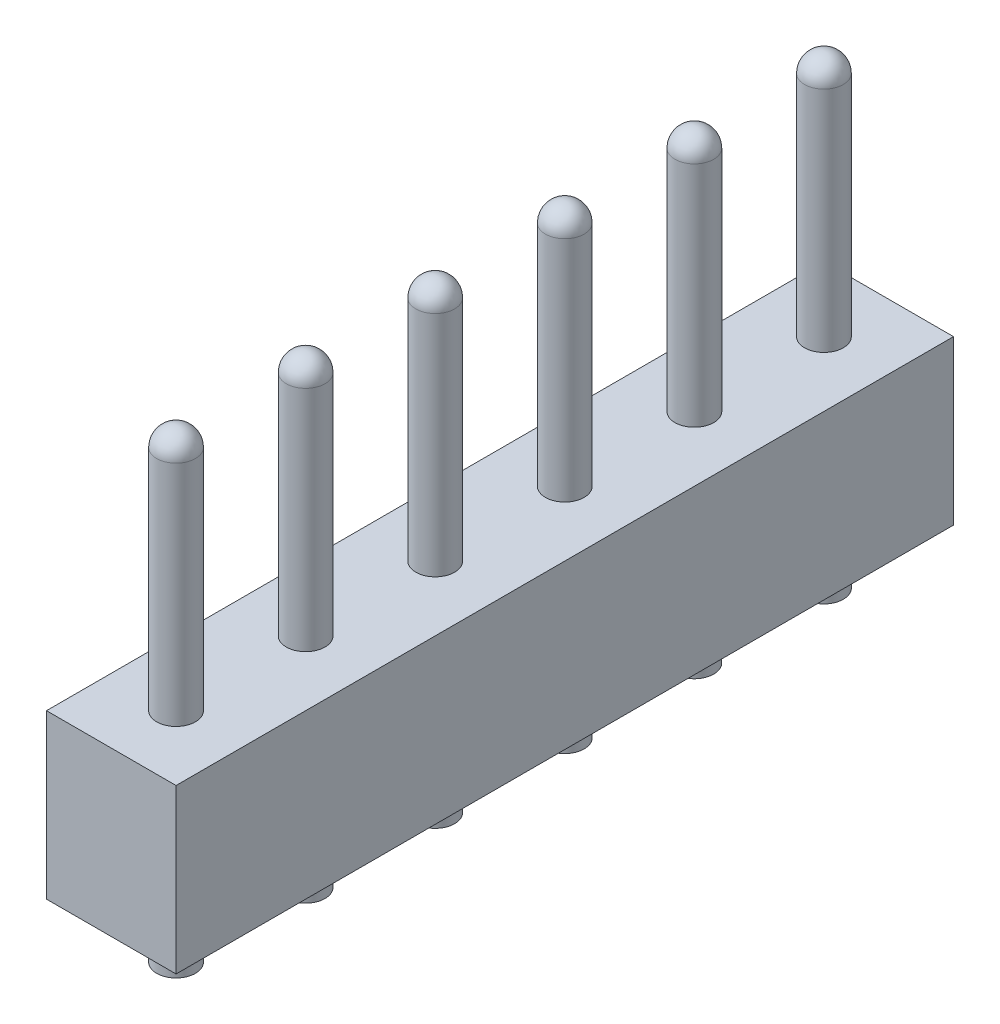
SolidWorks part; units mm, degrees
ref_plane "Płaszczyzna przednia" through (0, 0, 0) normal (0, 0, 1) x (1, 0, 0)
ref_plane "Płaszczyzna górna" through (0, 0, 0) normal (0, 1, 0) x (1, 0, 0)
ref_plane "Płaszczyzna prawa" through (0, 0, 0) normal (1, 0, 0) x (0, 0, -1)
sketch "Szkic1" plane through (0, 0, 0) normal (0, 1, 0) x (1, 0, 0)
  line L1 (1.27, -1.27) -> (-1.27, -1.27)
  line L2 (1.27, -1.27) -> (1.27, 1.27)
  line L3 (1.27, 1.27) -> (-1.27, 1.27)
  line L4 (-1.27, -1.27) -> (-1.27, 1.27)
  line L5 (1.27, -1.27) -> (-1.27, 1.27) construction
  line L6 (1.27, 1.27) -> (-1.27, -1.27) construction
  point P0 (0, 0)
  dimension "D1" = 2.54
  dimension "D2" = 2.54
extrude "Dodanie-wyciągnięcie1" add sketch "Szkic1" along normal blind 3.2
sketch "Szkic2" plane through (0, 3.2, 0) normal (0, 1, 0) x (1, 0, 0)
  circle A0 centre (0, 0) radius 0.38
extrude "Dodanie-wyciągnięcie3" add sketch "Szkic2" along normal blind 4.47
sketch "Szkic3" plane through (0, 7.67, 0) normal (0, 1, 0) x (1, 0, 0)
  line L0 (0, 0.38) -> (0, -0.38)
  arc A0 (0, -0.38) -> (0, 0.38) centre (0, 0) cw
  circle A1 centre (0, 0) radius 0.38 construction
revolve "Obrót2" add sketch "Szkic3" angle 180 about L0 reverse direction yes
sketch "Szkic4" plane through (0, 0, 0) normal (0, -1, 0) x (1, 0, 0)
  circle A0 centre (0, 0) radius 0.38
extrude "Dodanie-wyciągnięcie4" add sketch "Szkic4" along normal blind 1.07
pattern_linear "Szyk liniowy1" count 6 spacing 2.54 along (0, 0, -1) of "Dodanie-wyciągnięcie1", "Dodanie-wyciągnięcie3", "Obrót2", "Dodanie-wyciągnięcie4"
